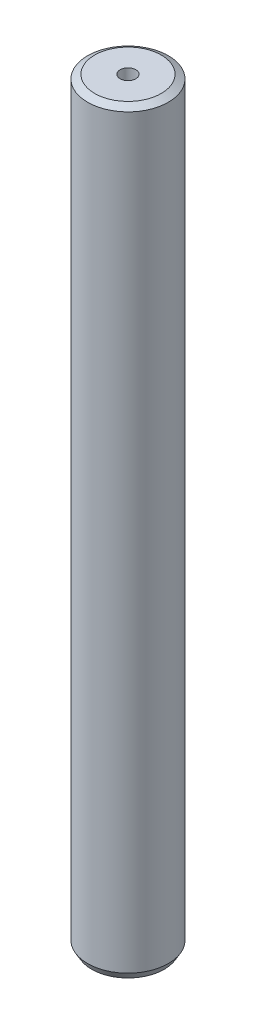
SolidWorks part; units mm, degrees
ref_plane "Front Plane" through (0, 0, 0) normal (0, 0, 1) x (1, 0, 0)
ref_plane "Top Plane" through (0, 0, 0) normal (0, 1, 0) x (1, 0, 0)
ref_plane "Right Plane" through (0, 0, 0) normal (1, 0, 0) x (0, 0, -1)
sketch "Sketch1" plane through (0, 0, 0) normal (0, 1, 0) x (1, 0, 0)
  circle A0 centre (0, 0) radius 5
  dimension "SHAFT_OD" = 10
extrude "Boss-Extrude1" add sketch "Sketch1" along normal blind 93.7816
sketch "Sketch2" plane through (0, 0, 0) normal (0, 1, 0) x (1, 0, 0)
  circle A0 centre (0, 0) radius 0.9716
  dimension "BORE_D" = 1.9431
extrude "Cut-Extrude1" cut sketch "Sketch2" along normal through all
chamfer "Chamfer1" distance 0.5049 angle 60 2 edges at (0, 93.7816, 5) (0, 0, 5) first distance on face at (0, 93.7816, 5) first distance on face at (0, 0, 0.9716)
